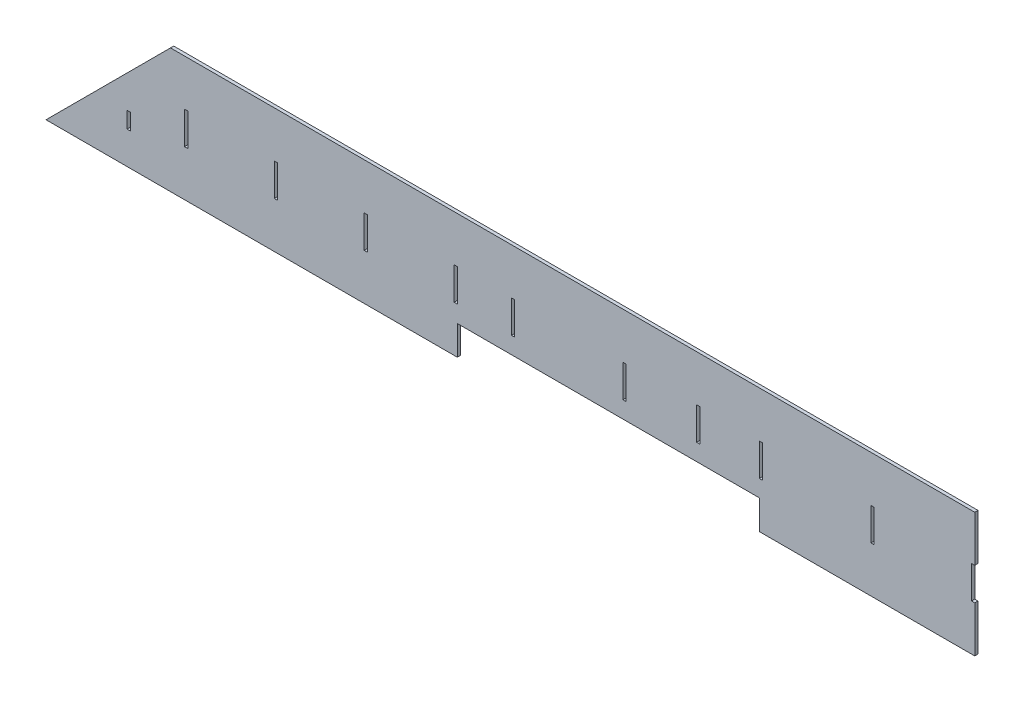
SolidWorks part; units mm, degrees
ref_plane "Front Plane" through (0, 0, 0) normal (0, 0, 1) x (1, 0, 0)
ref_plane "Top Plane" through (0, 0, 0) normal (0, 1, 0) x (1, 0, 0)
ref_plane "Right Plane" through (0, 0, 0) normal (1, 0, 0) x (0, 0, -1)
sketch "Sketch1" plane through (0, 0, 0) normal (0, 0, 1) x (1, 0, 0)
  line L0 (0, 0) -> (115, 115)
  line L1 (115, 115) -> (858, 115)
  line L3 (858, 0) -> (0, 0)
  line L4 (1244.614, 57.5) -> (-683.0281, 57.5) construction
  line L5 (128, 72.5) -> (131, 72.5)
  line L6 (128, 72.5) -> (128, 42.5)
  line L7 (128, 42.5) -> (131, 42.5)
  line L8 (131, 72.5) -> (131, 42.5)
  line L9 (75, 45) -> (78, 45)
  line L10 (75, 45) -> (75, 30)
  line L11 (75, 30) -> (78, 30)
  line L12 (78, 45) -> (78, 30)
  line L14 (211, 72.5) -> (214, 72.5)
  line L15 (211, 72.5) -> (211, 42.5)
  line L16 (211, 42.5) -> (214, 42.5)
  line L17 (214, 72.5) -> (214, 42.5)
  line L18 (294, 72.5) -> (297, 72.5)
  line L19 (294, 72.5) -> (294, 42.5)
  line L20 (294, 42.5) -> (297, 42.5)
  line L21 (297, 72.5) -> (297, 42.5)
  line L22 (377, 72.5) -> (380, 72.5)
  line L23 (377, 72.5) -> (377, 42.5)
  line L24 (377, 42.5) -> (380, 42.5)
  line L25 (380, 72.5) -> (380, 42.5)
  line L26 (430, 72.5) -> (433, 72.5)
  line L27 (430, 72.5) -> (430, 42.5)
  line L28 (430, 42.5) -> (433, 42.5)
  line L29 (433, 72.5) -> (433, 42.5)
  line L30 (533, 72.5) -> (536, 72.5)
  line L31 (533, 72.5) -> (533, 42.5)
  line L32 (533, 42.5) -> (536, 42.5)
  line L33 (536, 72.5) -> (536, 42.5)
  line L34 (601, 72.5) -> (604, 72.5)
  line L35 (601, 72.5) -> (601, 42.5)
  line L36 (601, 42.5) -> (604, 42.5)
  line L37 (604, 72.5) -> (604, 42.5)
  line L38 (659, 72.5) -> (662, 72.5)
  line L39 (659, 72.5) -> (659, 42.5)
  line L40 (659, 42.5) -> (662, 42.5)
  line L41 (662, 72.5) -> (662, 42.5)
  line L42 (762, 72.5) -> (765, 72.5)
  line L43 (762, 72.5) -> (762, 42.5)
  line L44 (762, 42.5) -> (765, 42.5)
  line L45 (765, 72.5) -> (765, 42.5)
  line L46 (855, 72.5) -> (858, 72.5)
  line L47 (855, 72.5) -> (855, 42.5)
  line L48 (855, 42.5) -> (858, 42.5)
  line L53 (858, 72.5) -> (858, 115)
  line L54 (858, 42.5) -> (858, 0)
  line L55 (75, 75) -> (75, 0) construction
  point P43 (855, 57.5)
  point P48 (75, 37.5)
  dimension "D1" = 115
  dimension "D2" = 30
  dimension "D3" = 3
  dimension "D4" = 15
  dimension "D5" = 3
  dimension "D6" = 75
  dimension "D7" = 50
  dimension "D8" = 30
  dimension "D9" = 3
  dimension "D10" = 30
  dimension "D11" = 3
  dimension "D12" = 80
  dimension "D13" = 80
  dimension "D14" = 80
  dimension "D15" = 3
  dimension "D16" = 30
  dimension "D17" = 50
  dimension "D18" = 3
  dimension "D19" = 30
  dimension "D20" = 100
  dimension "D21" = 3
  dimension "D22" = 30
  dimension "D23" = 65
  dimension "D24" = 30
  dimension "D25" = 3
  dimension "D26" = 55
  dimension "D27" = 3
  dimension "D28" = 30
  dimension "D29" = 3
  dimension "D30" = 30
  dimension "D31" = 100
  dimension "D32" = 90
  dimension "D33" = 3
  dimension "D34" = 30
  dimension "D35" = 45
extrude "Boss-Extrude1" add sketch "Sketch1" along normal blind 3
sketch "Sketch2" plane through (0, 0, 3) normal (0, 0, 1) x (1, 0, 0)
  line L0 (0, 0) -> (858, 0) construction
  line L1 (380, 0) -> (659, 0)
  line L2 (380, 0) -> (380, 27)
  line L3 (380, 27) -> (659, 27)
  line L4 (659, 0) -> (659, 27)
  line L6 (380, 42.5) -> (380, 72.5) construction
  line L7 (659, 72.5) -> (659, 42.5) construction
  dimension "D1" = 27
extrude "Cut-Extrude1" cut sketch "Sketch2" against normal blind 10
